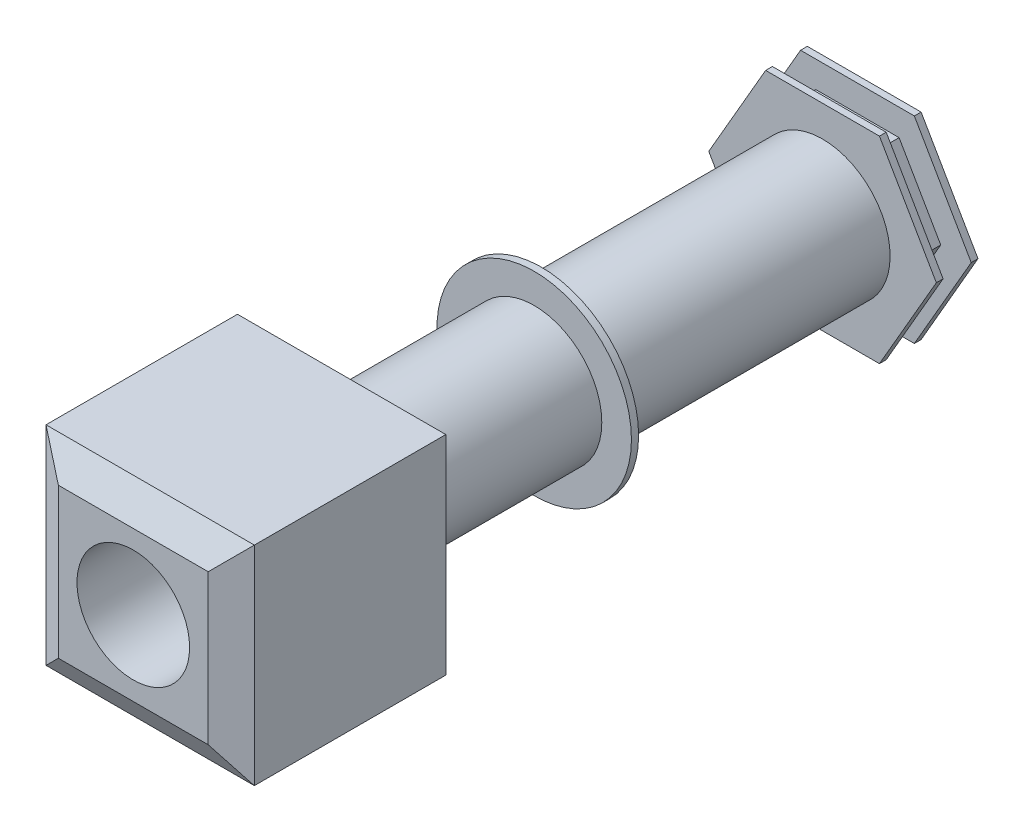
SolidWorks part; units mm, degrees
ref_plane "Front Plane" through (0, 0, 0) normal (0, 0, 1) x (1, 0, 0)
ref_plane "Top Plane" through (0, 0, 0) normal (0, 1, 0) x (1, 0, 0)
ref_plane "Right Plane" through (0, 0, 0) normal (1, 0, 0) x (0, 0, -1)
sketch "Sketch1" plane through (0, 0, 0) normal (0, 0, 1) x (1, 0, 0)
  line L1 (202.0726, 0) -> (101.0363, 175)
  line L2 (101.0363, 175) -> (-101.0363, 175)
  line L3 (-101.0363, 175) -> (-202.0726, 0)
  line L4 (-202.0726, 0) -> (-101.0363, -175)
  line L5 (-101.0363, -175) -> (101.0363, -175)
  line L6 (101.0363, -175) -> (202.0726, 0)
  circle A0 centre (0, 0) radius 175 construction
extrude "Boss-Extrude1" add sketch "Sketch1" along normal blind 12
sketch "Sketch2" plane through (0, 0, 12) normal (0, 0, 1) x (1, 0, 0)
  line L1 (147.8875, 0) -> (73.9437, 128.0743)
  line L2 (73.9437, 128.0743) -> (-73.9437, 128.0743)
  line L3 (-73.9437, 128.0743) -> (-147.8875, 0)
  line L4 (-147.8875, 0) -> (-73.9437, -128.0743)
  line L5 (-73.9437, -128.0743) -> (73.9437, -128.0743)
  line L6 (73.9437, -128.0743) -> (147.8875, 0)
  circle A0 centre (0, 0) radius 128.0743 construction
extrude "Boss-Extrude2" add sketch "Sketch2" along normal blind 50
sketch "Sketch3" plane through (0, 0, 62) normal (0, 0, 1) x (1, 0, 0)
  line L1 (202.0726, 0) -> (101.0363, 175)
  line L2 (101.0363, 175) -> (-101.0363, 175)
  line L3 (-101.0363, 175) -> (-202.0726, 0)
  line L4 (-202.0726, 0) -> (-101.0363, -175)
  line L5 (-101.0363, -175) -> (101.0363, -175)
  line L6 (101.0363, -175) -> (202.0726, 0)
  circle A0 centre (0, 0) radius 175 construction
extrude "Boss-Extrude3" add sketch "Sketch3" along normal blind 12
sketch "Sketch4" plane through (0, 0, 74) normal (0, 0, 1) x (1, 0, 0)
  circle A0 centre (0, 0) radius 120
extrude "Boss-Extrude4" add sketch "Sketch4" along normal blind 500
sketch "Sketch5" plane through (0, 0, 574) normal (0, 0, 1) x (1, 0, 0)
  circle A0 centre (0, 0) radius 172.6469
extrude "Boss-Extrude5" add sketch "Sketch5" along normal blind 12
chamfer "Chamfer1" distance 10 angle 80 1 edges at (120, 0, 574) first distance on face at (120, 0, 574)
sketch "Sketch6" plane through (0, 0, 586) normal (0, 0, 1) x (1, 0, 0)
  circle A0 centre (0, 0) radius 120
extrude "Boss-Extrude6" add sketch "Sketch6" along normal blind 330
sketch "Sketch8" plane through (0, 0, 916) normal (0, 0, 1) x (1, 0, 0)
  circle A0 centre (0, 0) radius 172.6469
extrude "Boss-Extrude7" add sketch "Sketch8" along normal blind 12
chamfer "Chamfer2" distance 6 angle 70 1 edges at (120, 0, 916) first distance on face at (120, 0, 916)
sketch "Sketch9" plane through (0, 0, 928) normal (0, 0, 1) x (1, 0, 0)
  line L1 (-185, 185) -> (185, 185)
  line L2 (-185, 185) -> (-185, -185)
  line L3 (-185, -185) -> (185, -185)
  line L4 (185, 185) -> (185, -185)
  line L5 (-185, 185) -> (185, -185) construction
  line L6 (-185, -185) -> (185, 185) construction
  point P0 (0, 0)
extrude "Boss-Extrude8" add sketch "Sketch9" along normal blind 370
sketch "Sketch10" plane through (0, 0, 1298) normal (0, 0, 1) x (1, 0, 0)
  circle A0 centre (0, 0) radius 100
extrude "Cut-Extrude1" cut sketch "Sketch10" against normal blind 900
chamfer "Chamfer3" distance 30 angle 60 4 edges at (185, 0, 1298) (0, -185, 1298) (-185, 0, 1298) (0, 185, 1298) first distance on face at (185, 0, 1113) first distance on face at (0, -185, 1113) first distance on face at (-185, 0, 1113) first distance on face at (0, 185, 1113)
